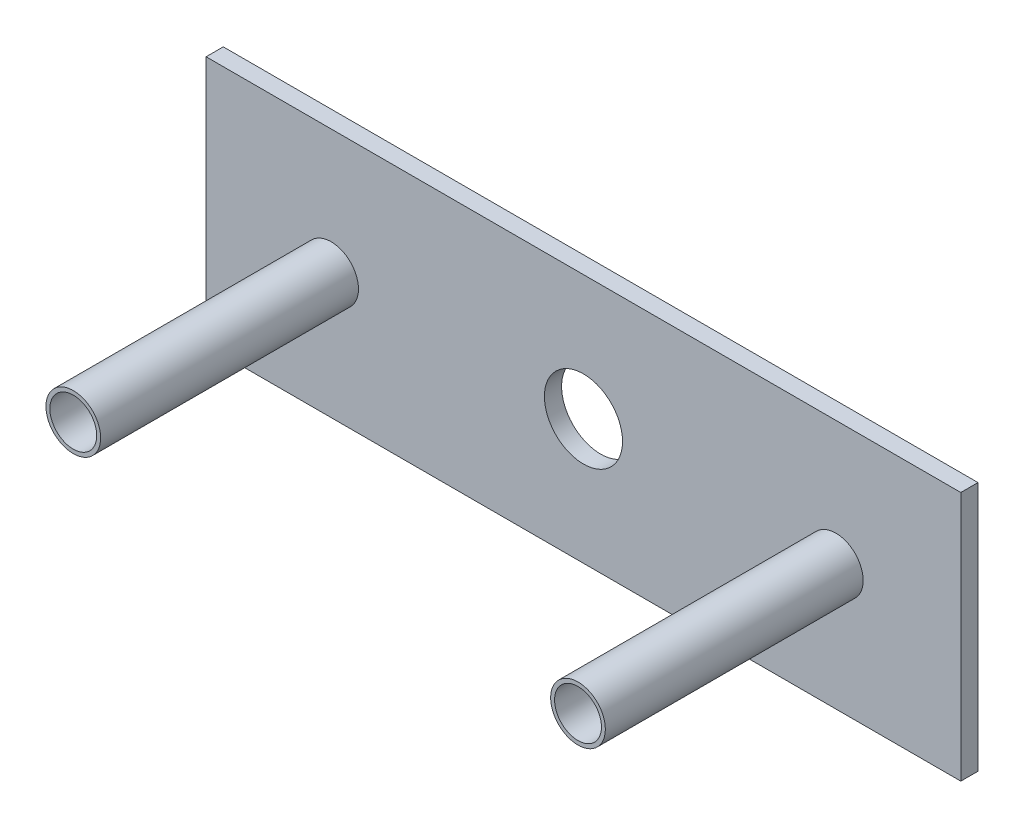
SolidWorks part; units mm, degrees
ref_plane "Plan de face" through (0, 0, 0) normal (0, 0, 1) x (1, 0, 0)
ref_plane "Plan de dessus" through (0, 0, 0) normal (0, 1, 0) x (1, 0, 0)
ref_plane "Plan de droite" through (0, 0, 0) normal (1, 0, 0) x (0, 0, -1)
sketch "Esquisse1" plane through (0, 0, 0) normal (0, 0, 1) x (1, 0, 0)
  line L1 (-47.6288, 18.2599) -> (48.9712, 18.2599)
  line L2 (-47.6288, 18.2599) -> (-47.6288, -13.7401)
  line L3 (-47.6288, -13.7401) -> (48.9712, -13.7401)
  line L4 (48.9712, 18.2599) -> (48.9712, -13.7401)
  dimension "D1" = 96.6
  dimension "D2" = 32
extrude "Boss.-Extru.1" add sketch "Esquisse1" along normal blind 2.2
sketch "Esquisse6" plane through (0, 0, 2.2) normal (0, 0, 1) x (1, 0, 0)
  line L0 (-47.6288, 18.2599) -> (-47.6288, -13.7401) construction
  line L3 (48.9712, 18.2599) -> (-47.6288, 18.2599) construction
  line L4 (48.9712, -13.7401) -> (48.9712, 18.2599) construction
  circle A0 centre (-31.6288, 2.2599) radius 3.5
  circle A1 centre (32.9712, 2.2599) radius 3.5
  dimension "D1" = 7
  dimension "D4" = 7
  dimension "D2" = 16
  dimension "D3" = 16
  dimension "D5" = 16
  dimension "D6" = 16
extrude "Boss.-Extru.2" add sketch "Esquisse6" along normal blind 33
sketch "Esquisse7" plane through (0, 0, 35.2) normal (0, 0, 1) x (1, 0, 0)
  line L1 (-47.6288, 18.2599) -> (-47.6288, -13.7401) construction
  line L3 (48.9712, 18.2599) -> (-47.6288, 18.2599) construction
  line L4 (48.9712, -13.7401) -> (48.9712, 18.2599) construction
  line L5 (-47.6288, -13.7401) -> (48.9712, -13.7401) construction
  circle A0 centre (-31.6288, 2.2599) radius 3
  circle A1 centre (32.9712, 2.2599) radius 3
  circle A2 centre (0.6712, 2.2599) radius 5
  dimension "D1" = 6
  dimension "D4" = 6
  dimension "D7" = 10
  dimension "D2" = 16
  dimension "D3" = 16
  dimension "D5" = 16
  dimension "D6" = 16
  dimension "D8" = 16
  dimension "D9" = 48.3
extrude "Enlèv. mat.-Extru.1" cut sketch "Esquisse7" against normal through all
